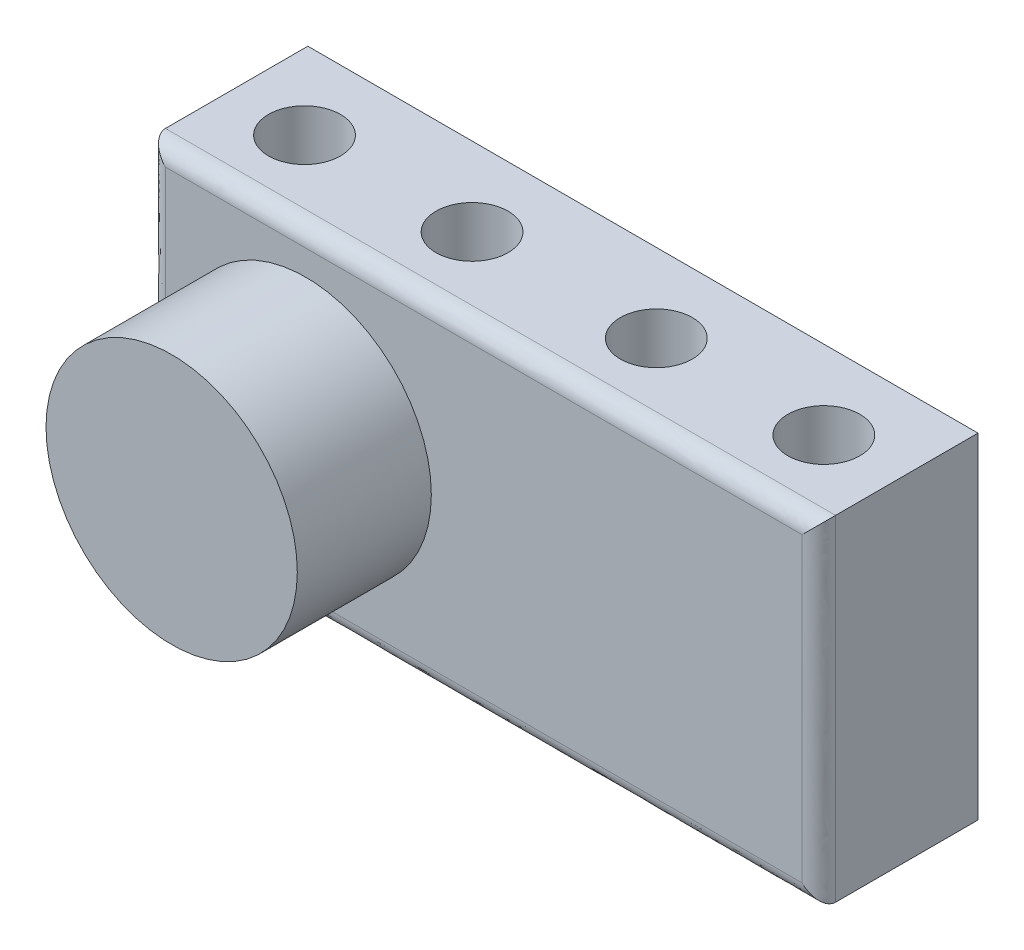
SolidWorks part; units mm, degrees
material "petg 20%"
ref_plane "Front Plane" through (0, 0, 0) normal (0, 0, 1) x (1, 0, 0)
ref_plane "Top Plane" through (0, 0, 0) normal (0, 1, 0) x (1, 0, 0)
ref_plane "Right Plane" through (0, 0, 0) normal (1, 0, 0) x (0, 0, -1)
sketch "Sketch1" plane through (0, 0, 0) normal (0, 0, 1) x (1, 0, 0)
  line L1 (-20, 10) -> (20, 10)
  line L2 (-20, 10) -> (-20, -10)
  line L3 (-20, -10) -> (20, -10)
  line L4 (20, 10) -> (20, -10)
  line L5 (-20, 10) -> (20, -10) construction
  line L6 (-20, -10) -> (20, 10) construction
  point P0 (0, 0)
  dimension "D1" = 40
  dimension "D2" = 20
extrude "Boss-Extrude1" add sketch "Sketch1" along normal blind 9.5
fillet "Fillet1" radius 1 4 edges at (0, -10, 9.5) (20, 0, 9.5) (0, 10, 9.5) (-20, 0, 9.5) first distance on face at (0, -10, 4.75) first distance on face at (20, 0, 4.75) first distance on face at (0, 10, 4.75) first distance on face at (-20, 0, 4.75)
sketch "Sketch4" plane through (0, 0, 9.5) normal (0, 0, 1) x (1, 0, 0)
  circle A0 centre (-10.6286, 0) radius 7.5
  dimension "D1" = 15
extrude "Boss-Extrude2" add sketch "Sketch4" along normal blind 8
sketch "Sketch5" plane through (0, -10, 0) normal (0, -1, 0) x (1, 0, 0)
  circle A0 centre (-15.5, 4.7) radius 2.15
  circle A1 centre (-5.5, 4.7) radius 2.15
  circle A2 centre (5.5, 4.7) radius 2.15
  circle A3 centre (15.5, 4.7) radius 2.15
  dimension "D1" = 4.3
  dimension "D2" = 4.3
  dimension "D3" = 4.3
  dimension "D4" = 4.3
extrude "Cut-Extrude1" cut sketch "Sketch5" against normal through all
